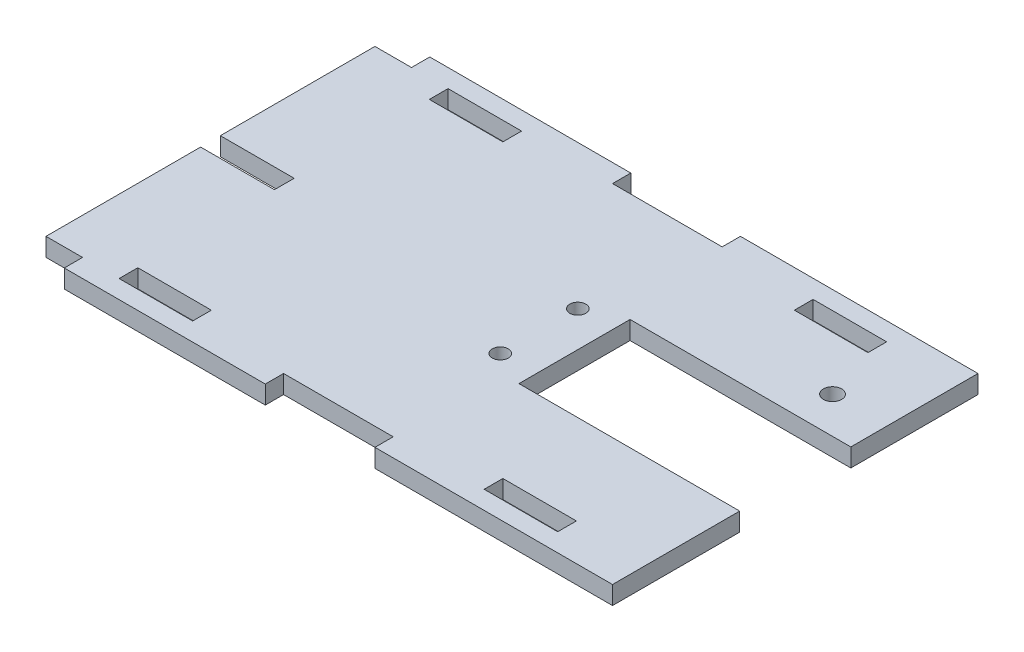
SolidWorks part; units mm, degrees
ref_plane "Front Plane" through (0, 0, 0) normal (0, 0, 1) x (1, 0, 0)
ref_plane "Top Plane" through (0, 0, 0) normal (0, 1, 0) x (1, 0, 0)
ref_plane "Right Plane" through (0, 0, 0) normal (1, 0, 0) x (0, 0, -1)
sketch "Sketch1" plane through (0, 0, 0) normal (0, 1, 0) x (1, 0, 0)
  line L0 (0, 63.5) -> (203.2, 63.5) construction
  line L1 (0, 0) -> (203.2, 0)
  line L2 (0, 0) -> (0, 60.071)
  line L3 (0, 127) -> (203.2, 127)
  line L4 (203.2, 0) -> (203.2, 44.196)
  line L5 (202.946, 82.55) -> (126.746, 82.55) construction
  line L7 (202.946, 44.45) -> (126.746, 44.45) construction
  line L8 (126.746, 82.55) -> (126.746, 44.45) construction
  line L9 (203.2, 82.804) -> (126.492, 82.804)
  line L10 (126.492, 82.804) -> (126.492, 44.196)
  line L11 (203.2, 44.196) -> (126.492, 44.196)
  line L12 (203.2, 60.579) -> (203.2, 53.721)
  line L13 (0, 66.929) -> (25.654, 66.929)
  line L14 (0, 66.675) -> (25.4, 66.675) construction
  line L16 (0, 60.325) -> (25.4, 60.325) construction
  line L17 (25.4, 66.675) -> (25.4, 60.325) construction
  line L22 (25.654, 66.929) -> (25.654, 60.071)
  line L23 (0, 60.071) -> (25.654, 60.071)
  line L27 (0, 66.929) -> (0, 127)
  line L28 (203.2, 82.804) -> (203.2, 127)
  line L29 (203.2, 53.721) -> (203.2, 60.579)
  line L30 (203.2, 82.804) -> (203.2, 44.196) construction
  line L31 (202.946, 82.55) -> (202.946, 44.45) construction
  dimension "D1" = 203.2
  dimension "D2" = 127
  dimension "D4" = 38.1
  dimension "D5" = 76.2
  dimension "D9" = 25.4
  dimension "D10" = 6.35
  dimension "D6" = 0.254
  dimension "D11" = 0.254
extrude "Boss-Extrude1" add sketch "Sketch1" along normal blind 6.35 contours L28 L3 L27 L13 L22 L23 L2 L1 L4 L11 L10 L9 region at (94.0263, 0, -63.5)
sketch "Sketch4" plane through (0, 6.35, 0) normal (0, 1, 0) x (1, 0, 0)
  line L1 (25.4762, 6.4262) -> (50.8762, 6.4262) construction
  line L2 (25.4762, 6.4262) -> (25.4762, 12.7762) construction
  line L3 (25.4762, 12.7762) -> (50.8762, 12.7762) construction
  line L4 (50.8762, 6.4262) -> (50.8762, 12.7762) construction
  line L6 (101.6, 0) -> (101.6, 127) construction
  line L8 (0, 63.5) -> (196.85, 63.5) construction
  line L9 (0, 66.929) -> (0, 60.071)
  line L16 (152.3238, 6.4262) -> (152.3238, 12.7762) construction
  line L17 (177.7238, 12.7762) -> (152.3238, 12.7762) construction
  line L18 (177.7238, 6.4262) -> (177.7238, 12.7762) construction
  line L19 (177.7238, 6.4262) -> (152.3238, 6.4262) construction
  line L20 (177.7238, 120.5738) -> (152.3238, 120.5738) construction
  line L21 (177.7238, 120.5738) -> (177.7238, 114.2238) construction
  line L22 (177.7238, 114.2238) -> (152.3238, 114.2238) construction
  line L23 (152.3238, 120.5738) -> (152.3238, 114.2238) construction
  line L24 (50.8762, 120.5738) -> (50.8762, 114.2238) construction
  line L25 (25.4762, 114.2238) -> (50.8762, 114.2238) construction
  line L26 (25.4762, 120.5738) -> (25.4762, 114.2238) construction
  line L27 (25.4762, 120.5738) -> (50.8762, 120.5738) construction
  line L28 (50.9524, 120.65) -> (50.9524, 114.1476)
  line L29 (25.4, 114.1476) -> (50.9524, 114.1476)
  line L30 (25.4, 120.65) -> (25.4, 114.1476)
  line L31 (25.4, 120.65) -> (50.9524, 120.65)
  line L32 (177.8, 120.65) -> (152.2476, 120.65)
  line L33 (152.2476, 120.65) -> (152.2476, 114.1476)
  line L34 (177.8, 114.1476) -> (152.2476, 114.1476)
  line L35 (177.8, 120.65) -> (177.8, 114.1476)
  line L36 (25.4, 6.35) -> (50.9524, 6.35)
  line L37 (50.9524, 6.35) -> (50.9524, 12.8524)
  line L38 (25.4, 12.8524) -> (50.9524, 12.8524)
  line L39 (25.4, 6.35) -> (25.4, 12.8524)
  line L40 (152.2476, 6.35) -> (152.2476, 12.8524)
  line L41 (177.8, 12.8524) -> (152.2476, 12.8524)
  line L42 (177.8, 6.35) -> (177.8, 12.8524)
  line L43 (177.8, 6.35) -> (152.2476, 6.35)
  line L44 (12.7, 127) -> (12.7, 120.65)
  line L45 (0, 0) -> (12.7, 0)
  line L46 (0, 0) -> (0, 6.35)
  line L47 (0, 6.35) -> (12.7, 6.35)
  line L48 (12.7, 0) -> (12.7, 6.35)
  line L49 (82.55, 0) -> (120.65, 0)
  line L50 (82.55, 0) -> (82.55, 6.35)
  line L51 (82.55, 6.35) -> (120.65, 6.35)
  line L52 (120.65, 0) -> (120.65, 6.35)
  line L53 (0, 120.65) -> (12.7, 120.65)
  line L54 (0, 127) -> (0, 120.65)
  line L55 (0, 127) -> (12.7, 127)
  line L56 (120.65, 127) -> (120.65, 120.65)
  line L57 (82.55, 120.65) -> (120.65, 120.65)
  line L58 (82.55, 127) -> (82.55, 120.65)
  line L59 (82.55, 127) -> (120.65, 127)
  line L60 (0, 66.929) -> (25.654, 66.929) construction
  line L61 (0, 60.071) -> (25.654, 60.071) construction
  line L62 (0, 0) -> (0, 60.071) construction
  line L63 (0, 0) -> (203.2, 0) construction
  dimension "D2" = 25.4
  dimension "D3" = 6.35
  dimension "D8" = 6.35
  dimension "D9" = 12.7
  dimension "D10" = 6.35
  dimension "D11" = 6.35
  dimension "D12" = 38.1
  dimension "D13" = 25.4
  dimension "D4" = 0.0762
  dimension "D5" = 0.0762
  dimension "D6" = 0.0762
  dimension "D7" = 0.0762
extrude "Cut-Extrude1" cut sketch "Sketch4" against normal through all contours L53 L44 | L31 L30 L29 L28 | L58 L57 L56 | L35 L32 L33 L34 | L43 L42 L41 L40 | L52 L51 L50 | L39 L36 L37 L38 | L48 L47 region at (38.1762, 6.35, -117.3988) region at (165.0238, 6.35, -117.3988) region at (38.1762, 6.35, -9.6012) region at (165.0238, 6.35, -9.6012) region at (6.35, 6.35, -123.825) region at (6.35, 6.35, -3.175) region at (101.6, 6.35, -3.175) region at (101.6, 6.35, -123.825)
sketch "Sketch5" plane through (0, 6.35, 0) normal (0, 1, 0) x (1, 0, 0)
  line L0 (203.2, 82.804) -> (126.492, 82.804) construction
  line L25 (203.2, 127) -> (120.65, 127)
  line L26 (120.65, 127) -> (120.65, 120.65)
  line L27 (120.65, 120.65) -> (82.55, 120.65)
  line L28 (82.55, 120.65) -> (82.55, 127)
  line L29 (82.55, 127) -> (12.7, 127)
  line L30 (12.7, 127) -> (12.7, 120.65)
  line L31 (12.7, 120.65) -> (0, 120.65)
  line L32 (0, 120.65) -> (0, 66.929)
  line L33 (0, 66.929) -> (25.654, 66.929)
  line L34 (25.654, 66.929) -> (25.654, 60.071)
  line L35 (25.654, 60.071) -> (0, 60.071)
  line L36 (0, 60.071) -> (0, 6.35)
  line L37 (0, 6.35) -> (12.7, 6.35)
  line L38 (12.7, 6.35) -> (12.7, 0)
  line L39 (12.7, 0) -> (82.55, 0)
  line L40 (82.55, 0) -> (82.55, 6.35)
  line L41 (82.55, 6.35) -> (120.65, 6.35)
  line L42 (120.65, 6.35) -> (120.65, 0)
  line L43 (120.65, 0) -> (203.2, 0)
  line L44 (203.2, 0) -> (203.2, 44.196)
  line L45 (203.2, 44.196) -> (126.492, 44.196)
  line L46 (126.492, 44.196) -> (126.492, 82.804)
  line L47 (126.492, 82.804) -> (203.2, 82.804)
  line L48 (203.2, 82.804) -> (203.2, 127)
  line L49 (203.2, 127) -> (120.65, 127) construction
  line L50 (120.65, 127) -> (120.65, 120.65) construction
  line L51 (120.65, 120.65) -> (82.55, 120.65) construction
  line L52 (82.55, 120.65) -> (82.55, 127) construction
  line L53 (82.55, 127) -> (12.7, 127) construction
  line L54 (12.7, 127) -> (12.7, 120.65) construction
  line L55 (12.7, 120.65) -> (0, 120.65) construction
  line L56 (0, 120.65) -> (0, 66.929) construction
  line L57 (0, 66.929) -> (25.654, 66.929) construction
  line L58 (25.654, 66.929) -> (25.654, 60.071) construction
  line L59 (25.654, 60.071) -> (0, 60.071) construction
  line L60 (0, 60.071) -> (0, 6.35) construction
  line L61 (0, 6.35) -> (12.7, 6.35) construction
  line L62 (12.7, 6.35) -> (12.7, 0) construction
  line L63 (12.7, 0) -> (82.55, 0) construction
  line L64 (82.55, 0) -> (82.55, 6.35) construction
  line L65 (82.55, 6.35) -> (120.65, 6.35) construction
  line L66 (120.65, 6.35) -> (120.65, 0) construction
  line L67 (120.65, 0) -> (203.2, 0) construction
  line L68 (203.2, 0) -> (203.2, 44.196) construction
  line L69 (203.2, 44.196) -> (126.492, 44.196) construction
  line L70 (126.492, 44.196) -> (126.492, 82.804) construction
  line L71 (126.492, 82.804) -> (203.2, 82.804) construction
  line L72 (203.2, 82.804) -> (203.2, 127) construction
  circle A0 centre (184.15, 95.504) radius 3.175
  dimension "D4" = 6.35
  dimension "D1" = 12.7
  dimension "D3" = 19.05
  dimension "D2" = 0
extrude "Cut-Extrude2" cut sketch "Sketch5" against normal through all
sketch "Sketch6" plane through (0, 0, 0) normal (0, -1, 0) x (1, 0, 0)
  line L0 (180.8055, 0) -> (180.8055, -127) construction
  line L1 (120.65, 0) -> (203.2, 0) construction
  line L2 (120.65, -127) -> (203.2, -127) construction
  line L3 (180.8055, -63.5) -> (71.8356, -63.5) construction
  circle A0 centre (114.173, -50.038) radius 2.7781
  circle A1 centre (114.173, -50.038) radius 2.54 construction
  circle A2 centre (114.173, -76.962) radius 2.7781
  dimension "D1" = 5.5562
extrude "Cut-Extrude3" cut sketch "Sketch6" against normal through all
